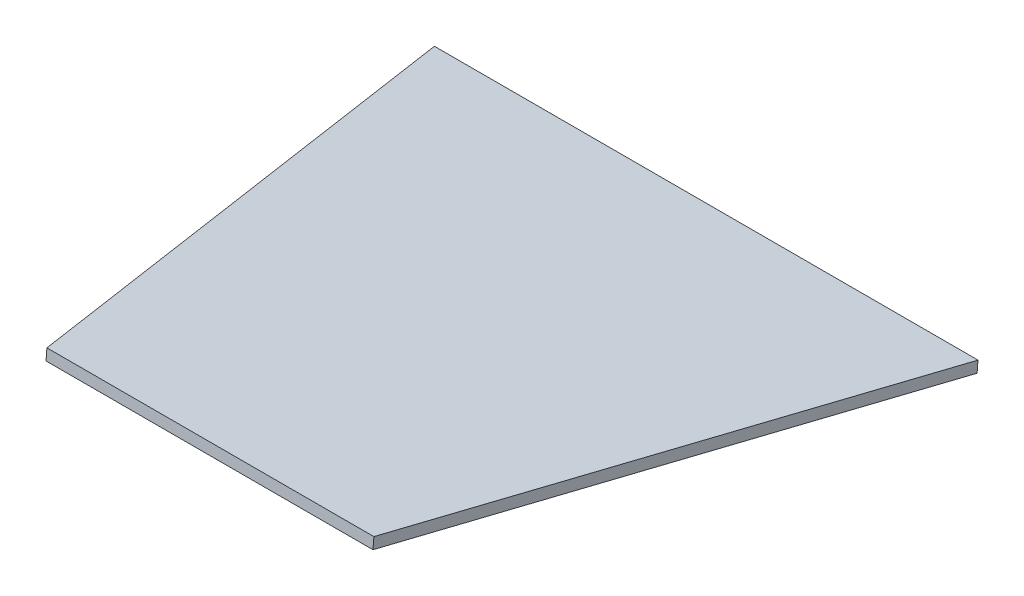
SolidWorks part; units mm, degrees
ref_plane "Front Plane" through (0, 0, 0) normal (0, 0, 1) x (1, 0, 0)
ref_plane "Top Plane" through (0, 0, 0) normal (0, 1, 0) x (1, 0, 0)
ref_plane "Right Plane" through (0, 0, 0) normal (1, 0, 0) x (0, 0, -1)
ref_plane "Plane1" through (-0.0001, -1306.6322, 107.7886) normal (0, -0.9966, 0.0822) x (-1, 0, 0)
sketch "Sketch1" plane through (-0.0001, -1306.6322, 107.7886) normal (0, -0.9966, 0.0822) x (-1, 0, 0)
  line L0 (927.9324, -1893.2884) -> (1306.8393, -1893.2884)
  line L1 (1306.8393, -1893.2884) -> (1432.3521, -1316.7398)
  line L2 (1432.3521, -1316.7398) -> (802.4196, -1316.7398)
  line L3 (802.4196, -1316.7398) -> (927.9324, -1893.2884)
  line L4 (802.4183, -1316.7398) -> (1432.3534, -1316.7398) construction
  line L5 (928.076, -1893.948) -> (801.0629, -1310.5075) construction
  line L6 (1433.7088, -1310.5075) -> (1306.6957, -1893.948) construction
  line L7 (1306.8419, -1893.2884) -> (927.9298, -1893.2884) construction
extrude "Boss-Extrude1" add sketch "Sketch1" along normal blind 12.7
